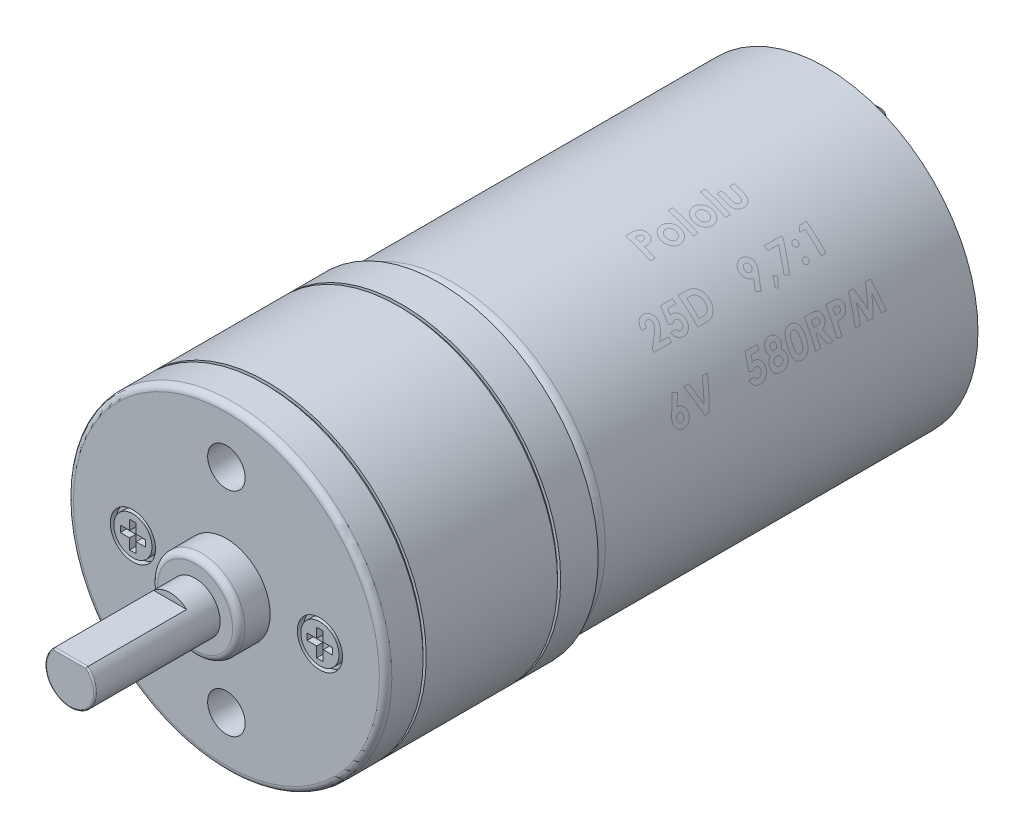
SolidWorks part; units mm, degrees
ref_plane "Plan de face" through (0, 0, 0) normal (0, 0, 1) x (1, 0, 0)
ref_plane "Plan de dessus" through (0, 0, 0) normal (0, 1, 0) x (1, 0, 0)
ref_plane "Plan de droite" through (0, 0, 0) normal (1, 0, 0) x (0, 0, -1)
sketch "Esquisse1" plane through (0, 0, 0) normal (1, 0, 0) x (0, 0, -1)
  line L0 (0, 0.0533) -> (96.8243, 0.0533) construction
  line L1 (-13.7537, 0.0533) -> (-75.4037, 0.0533)
  line L3 (-75.4037, 0.0533) -> (-75.4037, 2.0533)
  line L4 (-75.4037, 2.0533) -> (-65.4037, 2.0533)
  line L5 (-15.7537, 3.0533) -> (-13.7537, 3.0533)
  line L7 (-65.4037, 2.0533) -> (-65.4037, 3.5533)
  line L8 (-65.4037, 3.5533) -> (-62.9037, 3.5533)
  line L10 (-13.7537, 3.0533) -> (-13.7537, 0.0533)
  line L11 (-62.9037, 3.5533) -> (-62.9037, 12.7836)
  line L12 (-62.9037, 12.7836) -> (-59.9037, 12.7836)
  line L13 (-59.9037, 12.5336) -> (-59.9037, 12.7836)
  line L16 (-59.9037, 12.5336) -> (-59.6537, 12.5336)
  line L18 (-59.6537, 12.7836) -> (-49.1537, 12.7836)
  line L19 (-59.6537, 12.7836) -> (-59.6537, 12.5336)
  line L21 (-49.1537, 12.7836) -> (-49.1537, 12.5336)
  line L22 (-49.1537, 12.5336) -> (-48.9037, 12.5336)
  line L26 (-48.9037, 12.7836) -> (-45.9037, 12.7836)
  line L27 (-48.9037, 12.7836) -> (-48.9037, 12.5336)
  line L29 (-45.9037, 12.7836) -> (-45.9037, 11.2533)
  line L30 (-45.9037, 11.2533) -> (-45.8037, 11.2533)
  line L34 (-45.8037, 12.2533) -> (-15.0037, 12.2533)
  line L35 (-45.8037, 12.2533) -> (-45.8037, 11.2533)
  line L37 (-15.0037, 12.2533) -> (-15.0037, 11.2533)
  line L38 (-15.0037, 11.2533) -> (-15.7537, 11.2533)
  line L41 (-15.7537, 11.2533) -> (-15.7537, 3.0533)
  dimension "D1" = 1
  dimension "D2" = 0.1
  dimension "D3" = 1
  dimension "D4" = 0.25
  dimension "D5" = 0.25
  dimension "D6" = 0.25
  dimension "D7" = 0.25
  dimension "D8" = 2
  dimension "D9" = 10
  dimension "D10" = 0.75
  dimension "D11" = 3.5
  dimension "D12" = 17
  dimension "D13" = 2.5
  dimension "D14" = 12.2
  dimension "D15" = 3
  dimension "D16" = 30.8
  dimension "D17" = 3
  dimension "D18" = 3
  dimension "D19" = 2
revolve "Révolution1" add sketch "Esquisse1" angle 360 about L0
fillet "Congé1" radius 1 1 edges at (12.2, 0.0533, 45.8037)
fillet "Congé2" radius 0.5 1 edges at (3.5, 0.0533, 65.4037)
sketch "Esquisse2" plane through (0, 0, 75.4037) normal (0, 0, 1) x (1, 0, 0)
  line L0 (-1.3229, 1.5533) -> (1.3229, 1.5533)
  circle A0 centre (0, 0.0533) radius 2 construction
  circle A1 centre (0, 0.0533) radius 2 construction
  arc A2 (-1.3229, 1.5533) -> (1.3229, 1.5533) centre (0, 0.0533) cw
  dimension "D1" = 1.5
extrude "Enlèv. mat.-Extru.1" cut sketch "Esquisse2" against normal blind 8
fillet "Congé3" radius 0.125 2 edges at (0, -1.9467, 75.4037) (0, 1.5533, 75.4037)
sketch "Esquisse3" plane through (0, 0, 15.7537) normal (0, 0, -1) x (-1, 0, 0)
  line L0 (0, 6.7352) -> (0, 0) construction
  line L1 (-0.625, 8.2352) -> (0.625, 8.2352)
  line L2 (-0.625, 8.2352) -> (-0.625, 5.2352)
  line L3 (-0.625, 5.2352) -> (0.625, 5.2352)
  line L4 (0.625, 8.2352) -> (0.625, 5.2352)
  line L5 (-0.625, 6.7352) -> (0.625, 6.7352) construction
  line L6 (0, 0) -> (6.9335, 0) construction
  line L7 (0.625, -8.2352) -> (0.625, -5.2352)
  line L8 (-0.625, -5.2352) -> (0.625, -5.2352)
  line L9 (-0.625, -8.2352) -> (-0.625, -5.2352)
  line L10 (-0.625, -8.2352) -> (0.625, -8.2352)
  dimension "D1" = 1.25
  dimension "D2" = 3
extrude "Boss.-Extru.1" add sketch "Esquisse3" along normal blind 5
fillet "Congé4" radius 1.5 4 edges at (0, -8.2352, 10.7537) (0, -5.2352, 10.7537) (0, 5.2352, 10.7537) (0, 8.2352, 10.7537)
sketch "Esquisse4" plane through (0.625, 0, 0) normal (1, 0, 0) x (0, 0, -1)
  circle A0 centre (-12.2537, 6.7352) radius 0.75
  circle A1 centre (-12.2537, -6.7352) radius 0.75
  arc A2 (-10.7537, -6.7352) -> (-12.2537, -5.2352) centre (-12.2537, -6.7352) ccw construction
  arc A3 (-10.7537, 6.7352) -> (-12.2537, 8.2352) centre (-12.2537, 6.7352) ccw construction
  dimension "D1" = 1.5
  dimension "D2" = 1.5
extrude "Enlèv. mat.-Extru.2" cut sketch "Esquisse4" against normal blind 5
fillet "Congé5" radius 0.5 1 edges at (12.7303, 0.0533, 62.9037)
sketch "Esquisse5" plane through (0, 0, 0) normal (1, 0, 0) x (0, 0, -1)
  line L0 (-78.1511, 0) -> (0, 0) construction
ref_plane "Plan1" through (0, 0, 0) normal (0.7071, 0.7071, 0) x (-0.7071, 0.7071, 0)
sketch "Esquisse6" plane through (0, 0, 0) normal (0.7071, 0.7071, 0) x (-0.7071, 0.7071, 0)
  line L0 (4.1976, 38.5593) -> (4.1976, -1.4682) construction
  text T0 "<b>     Pololu </b>\r\n<b> 25D   9,7:1</b>\r\n<b>6V   580RPM</b>" font "Century Gothic" height in points 8
wrap "Enroulement1" sketch "Esquisse6" wrap type scribe source sketch "Esquisse6" face at (-12.2, 0.0533, 44.8037)
sketch "Esquisse7" plane through (0, 0, 62.9037) normal (0, 0, 1) x (1, 0, 0)
  line L0 (0, 8.5) -> (0, 0) construction
  line L1 (0, 0) -> (6.8936, 0) construction
  circle A0 centre (0, 8.5) radius 1.5
  circle A1 centre (0, -8.5) radius 1.5
  dimension "D1" = 3
extrude "Enlèv. mat.-Extru.3" cut sketch "Esquisse7" against normal blind 4
sketch "Esquisse8" plane through (0, 0, 62.9037) normal (0, 0, 1) x (1, 0, 0)
  line L0 (0, 7) -> (0, -7) construction
  line L1 (0, 0) -> (-7.4774, 0) construction
  line L2 (-7.222, 0.2425) -> (-6.4508, 0.2425)
  line L3 (-8.4855, 0.2425) -> (-7.7414, 0.2425)
  line L4 (-8.4855, 0.2425) -> (-8.4855, -0.2743)
  line L5 (-8.4855, -0.2743) -> (-7.7414, -0.2743)
  line L6 (-6.4508, 0.2425) -> (-6.4508, -0.2743)
  line L7 (-7.7414, 1.0184) -> (-7.222, 1.0184)
  line L8 (-7.7414, 1.0184) -> (-7.7414, 0.2425)
  line L9 (-7.7414, -1.1029) -> (-7.222, -1.1029)
  line L10 (-7.222, 1.0184) -> (-7.222, 0.2425)
  line L11 (-7.222, -0.2743) -> (-6.4508, -0.2743)
  line L12 (-7.7414, -0.2743) -> (-7.7414, -1.1029)
  line L13 (-7.222, -0.2743) -> (-7.222, -1.1029)
  line L14 (7.222, -0.2743) -> (7.222, -1.1029)
  line L15 (7.7414, -0.2743) -> (7.7414, -1.1029)
  line L16 (7.222, -0.2743) -> (6.4508, -0.2743)
  line L17 (7.222, 1.0184) -> (7.222, 0.2425)
  line L18 (7.7414, -1.1029) -> (7.222, -1.1029)
  line L19 (7.7414, 1.0184) -> (7.7414, 0.2425)
  line L20 (7.7414, 1.0184) -> (7.222, 1.0184)
  line L21 (6.4508, 0.2425) -> (6.4508, -0.2743)
  line L22 (8.4855, -0.2743) -> (7.7414, -0.2743)
  line L23 (8.4855, 0.2425) -> (8.4855, -0.2743)
  line L24 (8.4855, 0.2425) -> (7.7414, 0.2425)
  line L25 (7.222, 0.2425) -> (6.4508, 0.2425)
  circle A0 centre (0, 8.5) radius 1.5 construction
  circle A1 centre (0, -8.5) radius 1.5 construction
  circle A2 centre (-7.4774, 0) radius 1.8085
  circle A3 centre (-7.4774, 0) radius 1.5274
  circle A4 centre (7.4774, 0) radius 1.5274
  circle A5 centre (7.4774, 0) radius 1.8085
extrude "Enlèv. mat.-Extru.4" cut sketch "Esquisse8" against normal blind 0.5 contours L13 L11 L6 L2 L10 L7 L8 L3 L4 L5 L12 L9 | A2 A3 | L17 L25 L21 L16 L14 L18 L15 L22 L23 L24 L19 L20 | A5 A4 region at (-7.4742, -0.0313, 62.9037) region at (7.4742, -0.0313, 62.9037) region at (-9.2348, 0, 62.9037) region at (5.7201, 0, 62.9037)
